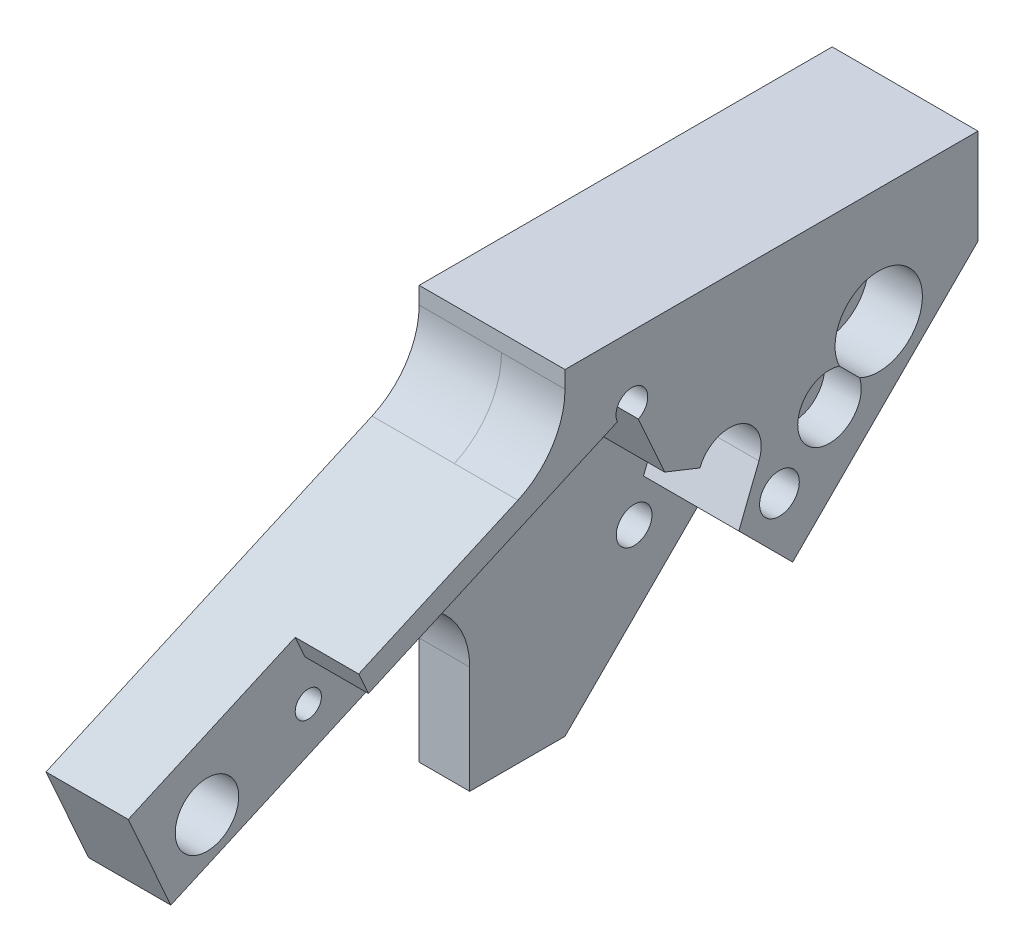
SolidWorks part; units mm, degrees
material "6061 合金"
ref_plane "前视基准面" through (0, 0, 0) normal (0, 0, 1) x (1, 0, 0)
ref_plane "上视基准面" through (0, 0, 0) normal (0, 1, 0) x (1, 0, 0)
ref_plane "右视基准面" through (0, 0, 0) normal (1, 0, 0) x (0, 0, -1)
sketch "草图1" plane through (0, 0, 0) normal (1, 0, 0) x (0, 0, -1)
  line L1 (-25, 25) -> (25, 25)
  line L2 (-25, 25) -> (-25, -25)
  line L3 (-25, -25) -> (25, -25)
  line L4 (25, 25) -> (25, -25)
  line L5 (-25, 25) -> (25, -25) construction
  line L6 (-25, -25) -> (25, 25) construction
  point P0 (0, 0)
  dimension "D1" = 50
  dimension "D2" = 50
extrude "凸台-拉伸1" add sketch "草图1" along normal offset from surface (15.3638 mm away) 8
sketch "草图2" plane through (0, 0, 0) normal (-1, 0, 0) x (0, 0, 1)
  line L0 (25, 25) -> (25, -25) construction
  line L1 (-25, 25) -> (25, 25) construction
  line L2 (25, 25) -> (25, -25)
  line L3 (-25, 25) -> (25, 25)
  line L4 (-25, 27) -> (27, 27)
  line L5 (27, 27) -> (27, -25)
  line L6 (-25, 27) -> (-25, 25)
  line L7 (27, -25) -> (25, -25)
  dimension "D1" = 2
extrude "凸台-拉伸2" add sketch "草图2" along normal blind 3 and the other way up to surface (15.3638 mm away) other way up to face at (15.3638, 0, 0)
sketch "草图3" plane through (-3, 0, 0) normal (-1, 0, 0) x (0, 0, 1)
  circle A0 centre (25, 25) radius 1
extrude "切除-拉伸1" cut sketch "草图3" against normal up to surface (3 mm away) up to face at (0, 0, 0)
sketch "草图4" plane through (15.3638, 0, 0) normal (1, 0, 0) x (0, 0, -1)
  circle A0 centre (0, 0) radius 2.2718
sketch "草图5" plane through (15.3638, 0, 0) normal (1, 0, 0) x (0, 0, -1)
  line L0 (-32.6169, 1.449) -> (-65.893, -13.3665) construction
  line L1 (-36.7494, 10.7306) -> (-70.0254, -4.0848) construction
  line L2 (-32.6169, 1.449) -> (-65.893, -13.3665)
  line L3 (-36.7494, 10.7306) -> (-70.0254, -4.0848)
  line L4 (25, -4.0848) -> (15.6172, 2.7629) construction
  line L5 (25, -25) -> (25, 27) construction
  line L6 (15.6172, 2.7629) -> (5.608, -7) construction
  line L7 (5.608, -7) -> (11.6662, -24.8793) construction
  line L8 (-27.1271, -24.8793) -> (22.3729, -24.8793) construction
  line L9 (-18.323, 18.2395) -> (-14.4489, 9.5379) construction
  line L10 (-18.323, 18.2395) -> (-14.4489, 9.5379)
  circle A0 centre (-64.0834, -7) radius 2.3812 construction
  circle A1 centre (-42.1556, 2.7629) radius 2.3812 construction
  circle A2 centre (-51.3212, -1.3179) radius 2.3813 construction
  circle A3 centre (-64.0834, -7) radius 2.3813
  circle A4 centre (-42.1556, 2.7629) radius 2.3813
  circle A5 centre (-51.3212, -1.3179) radius 2.3813
hole_wizard "M6 螺纹孔1" positions "3D草图1" profile "草图6" tap size "M6" standard "GB" end condition through all
sketch3d "3D草图1"
  point P0 (15.3638, 0, 0)
sketch "草图6" plane through (15.3638, 0, 0) normal (0, 1, 0) x (0, 0, -1)
  line L0 (0, 0) -> (0, 18.3638)
  line L1 (0, 18.3638) -> (2.5, 18.3638)
  line L2 (2.5, 18.3638) -> (2.5, 0)
  line L5 (2.5, 0) -> (0, 0)
  line L11 (0, -6.35) -> (0, 107.95) construction
  dimension "通孔螺纹孔钻头直径" = 5
  dimension "通孔螺纹孔钻头深度" = 18.3638
cosmetic thread "孔螺蚊线1" parameters "D2"=6
sketch "草图7" plane through (15.3638, 0, 0) normal (1, 0, 0) x (0, 0, -1)
  line L1 (-6.3, 6.3) -> (6.3, 6.3) construction
  line L2 (-6.3, 6.3) -> (-6.3, -6.3) construction
  line L3 (-6.3, -6.3) -> (6.3, -6.3) construction
  line L4 (6.3, 6.3) -> (6.3, -6.3) construction
  line L5 (-6.3, 6.3) -> (6.3, -6.3) construction
  line L6 (-6.3, -6.3) -> (6.3, 6.3) construction
  line L7 (-12.5, 12.5) -> (12.5, 12.5) construction
  line L8 (-12.5, 12.5) -> (-12.5, -12.5) construction
  line L9 (-12.5, -12.5) -> (12.5, -12.5) construction
  line L10 (12.5, 12.5) -> (12.5, -12.5) construction
  line L11 (-12.5, 12.5) -> (12.5, -12.5) construction
  line L12 (-12.5, -12.5) -> (12.5, 12.5) construction
  point P0 (0, 0)
  point P6 (0, 0)
  dimension "D1" = 12.6
  dimension "D2" = 25
hole_wizard "打孔尺寸(%根据)内六角圆柱头螺钉的类型2" positions "3D草图3" profile "草图8" counterbore size "M4" standard "GB" end condition through all
sketch3d "3D草图3"
  point P0 (15.3638, 6.3, -6.3)
  point P3 (15.3638, 6.3, 6.3)
  point P10 (15.3638, -6.3, 6.3)
sketch "草图8" plane through (15.3638, 6.3, -6.3) normal (0, 1, 0) x (0, 0, -1)
  line L0 (0, 0) -> (0, 18.3638)
  line L1 (0, 18.3638) -> (2.25, 18.3638)
  line L3 (2.25, 18.3638) -> (2.25, 4.6)
  line L4 (2.25, 4.6) -> (4, 4.6)
  line L5 (4, 4.6) -> (4, 0)
  line L7 (4, 0) -> (0, 0)
  line L11 (0, -6.35) -> (0, 107.95) construction
  dimension "通孔孔直径" = 4.5
  dimension "通孔孔深度" = 18.3638
  dimension "柱形沉头孔直径" = 8
  dimension "柱形沉头孔深度" = 4.6
hole_wizard "打孔尺寸(%根据)内六角圆柱头螺钉的类型2" positions "3D草图4" profile "草图9" counterbore size "M6" standard "GB" end condition through all
sketch3d "3D草图4"
  point P0 (15.3638, 12.5, -12.5)
sketch "草图9" plane through (15.3638, 12.5, -12.5) normal (0, 1, 0) x (0, 0, -1)
  line L0 (0, 0) -> (0, 18.3638)
  line L1 (0, 18.3638) -> (3.3, 18.3638)
  line L3 (3.3, 18.3638) -> (3.3, 6.8)
  line L4 (3.3, 6.8) -> (5.5, 6.8)
  line L5 (5.5, 6.8) -> (5.5, 0)
  line L7 (5.5, 0) -> (0, 0)
  line L11 (0, -6.35) -> (0, 107.95) construction
  dimension "通孔孔直径" = 6.6
  dimension "通孔孔深度" = 18.3638
  dimension "柱形沉头孔直径" = 11
  dimension "柱形沉头孔深度" = 6.8
sketch "草图10" plane through (15.3638, 0, 0) normal (1, 0, 0) x (0, 0, -1)
  line L0 (25, -25) -> (25, 15)
  line L1 (25, -25) -> (25, 27) construction
  line L2 (25, 15) -> (-15, -25)
  line L3 (-27, -25) -> (25, -25) construction
  line L4 (-15, -25) -> (25, -25)
  dimension "D1" = 40
extrude "切除-拉伸2" cut sketch "草图10" against normal through all
sketch "草图11" plane through (15.3638, 0, 0) normal (1, 0, 0) x (0, 0, -1)
  line L0 (-70.0254, -4.0848) -> (-65.893, -13.3665)
  line L1 (-65.893, -13.3665) -> (-27, 3.9498)
  line L2 (-27, -25) -> (-27, 27) construction
  line L3 (-27, 3.9498) -> (-27, 15.0713)
  line L4 (-27, 15.0713) -> (-70.0254, -4.0848)
extrude "凸台-拉伸3" add sketch "草图11" against normal up to surface (18.3638 mm away) up to face at (-3, 11.3153, 11.3153)
sketch "草图16" plane through (15.3638, 0, 0) normal (1, 0, 0) x (0, 0, -1)
  line L0 (-70.0254, -4.0848) -> (-65.893, -13.3665)
  line L1 (-70.0254, -4.0848) -> (-18.5813, 18.8196)
  line L2 (-65.893, -13.3665) -> (-14.4489, 9.5379)
  line L3 (-18.5813, 18.8196) -> (-14.4489, 9.5379)
  line L4 (-18.323, 18.2395) -> (-14.4489, 9.5379) construction
extrude "切除-拉伸3" cut sketch "草图16" against normal blind 8
hole_wizard "M4 螺纹孔1" positions "3D草图5" profile "草图12" tap size "M4" standard "GB" end condition through all
sketch3d "3D草图5"
  point P3 (15.3638, -1.3179, 51.3212)
  point P6 (15.3638, 2.7629, 42.1556)
sketch "草图12" plane through (15.3638, -1.3179, 51.3212) normal (0, 1, 0) x (0, 0, -1)
  line L0 (0, 0) -> (0, 18.3638)
  line L1 (0, 18.3638) -> (1.65, 18.3638)
  line L2 (1.65, 18.3638) -> (1.65, 0)
  line L5 (1.65, 0) -> (0, 0)
  line L11 (0, -6.35) -> (0, 107.95) construction
  dimension "通孔螺纹孔钻头直径" = 3.3
  dimension "通孔螺纹孔钻头深度" = 18.3638
cosmetic thread "孔螺蚊线2" parameters "D2"=4
cosmetic thread "孔螺蚊线3" parameters "D2"=4
fillet "圆角1" radius 10 1 edges at (2.1819, 3.9498, 27)
sketch "草图13" plane through (15.3638, 0, 0) normal (1, 0, 0) x (0, 0, -1)
  line L0 (-70.0254, -4.0848) -> (-65.893, -13.3665) construction
  line L1 (-70.0254, -4.0848) -> (-65.893, -13.3665)
  line L2 (-36.7494, 10.7306) -> (-70.0254, -4.0848) construction
  line L3 (-36.7494, 10.7306) -> (-70.0254, -4.0848)
  line L4 (-37.9696, 13.4712) -> (-73.9863, -2.5644)
  line L5 (-73.9863, -2.5644) -> (-68.6336, -14.5867)
  line L6 (-37.9696, 13.4712) -> (-36.7494, 10.7306)
  line L7 (-68.6336, -14.5867) -> (-65.893, -13.3665)
  dimension "D1" = 3
extrude "凸台-拉伸4" add sketch "草图13" against normal up to surface (18.3638 mm away) up to face at (-3, -1.3179, 49.6712)
sketch "草图17" plane through (7.3638, 0, 0) normal (1, 0, 0) x (0, 0, -1)
  line L0 (-18.5813, 18.8196) -> (-22.2235, 27)
  line L1 (-27, 27) -> (25, 27) construction
  line L2 (-22.2235, 27) -> (-27, 27)
  line L3 (-27, 27) -> (-27, 15.0713)
  line L4 (-27, 15.0713) -> (-18.5813, 18.8196)
  line L5 (-65.893, -13.3665) -> (-68.6336, -14.5867)
  line L6 (-65.893, -13.3665) -> (-71.6564, -0.4216)
  line L7 (-68.6336, -14.5867) -> (-74.397, -1.6418)
  line L8 (-71.6564, -0.4216) -> (-74.397, -1.6418)
extrude "切除-拉伸6" cut sketch "草图17" along normal through all
sketch "草图18" plane through (0, 13.3288, 5.9344) normal (0, 0.9135, 0.4067) x (1, 0, 0)
  line L1 (7.3638, -9.3203) -> (18.2882, -9.3203)
  line L2 (7.3638, -9.3203) -> (7.3638, -36.1151)
  line L3 (7.3638, -36.1151) -> (18.2882, -36.1151)
  line L4 (18.2882, -9.3203) -> (18.2882, -36.1151)
extrude "切除-拉伸8" cut sketch "草图18" against normal through all
sketch "草图19" plane through (7.3638, 0, 0) normal (1, 0, 0) x (0, 0, -1)
  line L0 (-12.5, -12.5) -> (12.5, -12.5) construction
hole_wizard "打孔尺寸(%根据)内六角圆柱头螺钉的类型3" [suppressed] positions "3D草图6" profile "草图20" counterbore size "M6" standard "GB"
sketch3d "3D草图6"
  point P0 (7.3638, -12.5, 12.5)
sketch "草图20" plane through (7.3638, -12.5, 12.5) normal (0, 1, 0) x (0, 0, -1)
  line L0 (0, 0) -> (0, 10.3638)
  line L1 (0, 10.3638) -> (3.3, 10.3638)
  line L3 (3.3, 10.3638) -> (3.3, 5)
  line L4 (3.3, 5) -> (5.5, 5)
  line L5 (5.5, 5) -> (5.5, 0)
  line L7 (5.5, 0) -> (0, 0)
  line L11 (0, -6.35) -> (0, 107.95) construction
  dimension "通孔孔直径" = 6.6
  dimension "通孔孔深度" = 10.3638
  dimension "柱形沉头孔直径" = 11
  dimension "柱形沉头孔深度" = 5
sketch "草图21" plane through (10.7638, 0, 0) normal (1, 0, 0) x (0, 0, -1)
  line L2 (-8.7909, -3.1702) -> (-8.0351, -4.8676)
  line L3 (-6.3965, -8.5479) -> (-5.6408, -10.2453)
  line L4 (-8.7909, -3.1702) -> (-8.0351, -4.8676)
  line L5 (-6.3965, -8.5479) -> (-5.6408, -10.2453)
  arc A2 (-5.6408, -10.2453) -> (-8.7909, -3.1702) centre (-6.3, -6.3) ccw
  arc A3 (-6.3965, -8.5479) -> (-8.0351, -4.8676) centre (-6.3, -6.3) ccw
  arc A4 (-5.6408, -10.2453) -> (-8.7909, -3.1702) centre (-6.3, -6.3) ccw
  arc A5 (-6.3965, -8.5479) -> (-8.0351, -4.8676) centre (-6.3, -6.3) ccw
  dimension "D1" = 0
extrude "切除-拉伸9" cut sketch "草图21" against normal up to surface (3.4 mm away) up to face at (7.3638, -1.3179, 52.9712)
sketch "草图22" plane through (7.3638, 0, 0) normal (1, 0, 0) x (0, 0, -1)
  line L0 (-38.814, -1.6147) -> (-14.4489, 9.5379)
  line L1 (-18.323, 18.2395) -> (-14.4489, 9.5379) construction
  line L2 (-14.4489, 9.5379) -> (-3.9786, -13.9786)
  line L3 (-3.9786, -13.9786) -> (-15, -25)
  line L4 (-15, -25) -> (-27, -25)
  line L5 (-27, -25) -> (-27, -11.4488)
  arc A0 (-27, -11.4488) -> (-38.814, -1.6147) centre (-37, -11.4488) ccw construction
  arc A1 (-27, -11.4488) -> (-38.814, -1.6147) centre (-37, -11.4488) ccw
extrude "切除-拉伸11" cut sketch "草图22" against normal blind 4
sketch "草图23" plane through (15.3638, 0, 0) normal (1, 0, 0) x (0, 0, -1)
  line L0 (-14.4489, 9.5379) -> (-6.3, 6.3)
  line L3 (-3.9786, -13.9786) -> (-14.4489, 9.5379)
  line L4 (-6.3, 6.3) -> (-2.5827, 4.8229)
  line L5 (-2.5827, 4.8229) -> (-5.1161, -1.5529)
  line L6 (-5.1161, -1.5529) -> (1.6655, -8.3345)
  line L7 (-3.9786, -13.9786) -> (1.6655, -8.3345)
  line L8 (25, 15) -> (-3.9786, -13.9786) construction
  circle A0 centre (-6.3, 6.3) radius 4 construction
  dimension "D1" = 33
extrude "切除-拉伸12" cut sketch "草图23" against normal up to surface (12 mm away) up to face at (3.3638, -9.8323, 17.4385)
sketch "草图24" plane through (10.7638, 0, 0) normal (1, 0, 0) x (0, 0, -1)
  line L1 (-10.0173, 7.7771) -> (-8.391, 7.1308)
  line L2 (-10.0173, 7.7771) -> (-8.391, 7.1308)
  line L4 (-4.209, 5.4692) -> (-2.5827, 4.8229)
  line L5 (-4.209, 5.4692) -> (-2.5827, 4.8229)
  arc A1 (-2.5827, 4.8229) -> (-10.0173, 7.7771) centre (-6.3, 6.3) ccw
  arc A2 (-2.5827, 4.8229) -> (-10.0173, 7.7771) centre (-6.3, 6.3) ccw
  arc A4 (-4.209, 5.4692) -> (-8.391, 7.1308) centre (-6.3, 6.3) ccw
  arc A5 (-4.209, 5.4692) -> (-8.391, 7.1308) centre (-6.3, 6.3) ccw
  dimension "D1" = 0
extrude "切除-拉伸13" cut sketch "草图24" against normal blind 4
sketch "草图25" plane through (0, -11.8798, 26.6826) normal (0, 0.4067, -0.9135) x (-1, 0, 0)
  line L5 (3, 24.7502) -> (3, 27.7502)
  line L6 (3, 27.7502) -> (-15.3638, 27.7502)
  line L7 (-15.3638, 27.7502) -> (-15.3638, 24.7502)
  line L8 (-15.3638, 24.7502) -> (-7.3638, 24.7502)
  line L9 (-7.3638, 24.7502) -> (3, 24.7502)
  line L10 (3, 24.7502) -> (3, 27.7502)
  line L11 (3, 27.7502) -> (-15.3638, 27.7502)
  line L12 (-15.3638, 27.7502) -> (-15.3638, 24.7502)
  line L13 (-15.3638, 24.7502) -> (-7.3638, 24.7502)
  line L15 (-7.3638, 24.7502) -> (3, 24.7502)
  dimension "D1" = 0
extrude "凸台-拉伸7" add sketch "草图25" along normal up to surface (10.672 mm away) up to face at (2.1819, 21.0357, 27)
fillet "圆角2" radius 10 1 edges at (2.1819, 18.3552, 27)
sketch "草图26" plane through (7.3638, 0, 0) normal (1, 0, 0) x (0, 0, -1)
  line L0 (-27, 15.0713) -> (-18.5813, 18.8196)
  line L1 (-18.5813, 18.8196) -> (-22.2235, 27)
  line L2 (-22.2235, 27) -> (-27, 27)
  line L4 (-27, 27) -> (-27, 24.8493)
  line L5 (-27, 18.3552) -> (-71.2456, -1.3442) construction
  line L6 (-27, 15.0713) -> (-27, 18.3552) construction
  line L7 (-27, 18.3552) -> (-71.2456, -1.3442)
  line L8 (-27, 15.0713) -> (-27, 18.3552)
  arc A0 (-32.9326, 15.7138) -> (-27, 24.8493) centre (-37, 24.8493) ccw construction
  arc A1 (-32.9326, 15.7138) -> (-27, 24.8493) centre (-37, 24.8493) ccw
  line M6 (-14.4489, 9.5379) -> (-22.2235, 27)
  line M7 (-22.2235, 27) -> (-27, 27)
  line M8 (-27, 27) -> (-27, 24.8493)
  arc M9 (-27, 24.8493) -> (-32.9326, 15.7138) centre (-37, 24.8493) cw
  line M10 (-32.9326, 15.7138) -> (-27, 18.3552)
  line M11 (-27, 18.3552) -> (-27, 15.0713)
extrude "凸台-拉伸8" add sketch "草图26" along normal up to surface (8 mm away) contours L0 M11 M6 M7 M8 M9 M10 up to face at (15.3638, 6.9994, 48.8178)
sketch "草图27" plane through (15.3638, 0, 0) normal (1, 0, 0) x (0, 0, -1)
  circle A0 centre (-18.5813, 18.8196) radius 2
extrude "切除-拉伸14" cut sketch "草图27" against normal up to surface (8 mm away) up to face at (7.3638, -1.3179, 52.9712)
sketch "草图28" plane through (7.3638, 0, 0) normal (1, 0, 0) x (0, 0, -1)
  circle A0 centre (-64.0834, -7) radius 2.3813 construction
  circle A1 centre (-64.0834, -7) radius 2.3813
hole_wizard "打孔尺寸(%根据)内六角圆柱头螺钉的类型4" positions "3D草图7" profile "草图29" counterbore size "M4" standard "GB" end condition through all
sketch3d "3D草图7"
  point P0 (7.3638, -7, 64.0834)
sketch "草图29" plane through (7.3638, -7, 64.0834) normal (0, 1, 0) x (0, 0, -1)
  line L0 (0, 0) -> (0, 10.3638)
  line L1 (0, 10.3638) -> (2.25, 10.3638)
  line L3 (2.25, 10.3638) -> (2.25, 6)
  line L4 (2.25, 6) -> (4, 6)
  line L5 (4, 6) -> (4, 0)
  line L7 (4, 0) -> (0, 0)
  line L11 (0, -6.35) -> (0, 107.95) construction
  dimension "通孔孔直径" = 4.5
  dimension "通孔孔深度" = 10.3638
  dimension "柱形沉头孔直径" = 8
  dimension "柱形沉头孔深度" = 6
sketch "草图30" plane through (15.3638, 0, 0) normal (1, 0, 0) x (0, 0, -1)
  line L11 (-17.7678, 16.9925) -> (-14.4489, 9.5379)
  line L12 (-14.4489, 9.5379) -> (-10.0173, 7.7771)
  line L13 (-2.5827, 4.8229) -> (-5.1161, -1.5529)
  line L14 (-5.1161, -1.5529) -> (1.6655, -8.3345)
  line L15 (1.6655, -8.3345) -> (25, 15)
  line L16 (25, 15) -> (25, 27)
  line L17 (25, 27) -> (-27, 27)
  line L18 (-27, 27) -> (-27, 24.8493)
  line L19 (-32.9326, 15.7138) -> (-71.2456, -1.3442)
  line L20 (-71.2456, -1.3442) -> (-70.0254, -4.0848)
  line L21 (-70.0254, -4.0848) -> (-20.4084, 18.0061)
  line L22 (-17.7678, 16.9925) -> (-14.4489, 9.5379)
  line L23 (-14.4489, 9.5379) -> (-10.0173, 7.7771)
  line L24 (-2.5827, 4.8229) -> (-5.1161, -1.5529)
  line L25 (-5.1161, -1.5529) -> (1.6655, -8.3345)
  line L26 (1.6655, -8.3345) -> (25, 15)
  line L27 (25, 15) -> (25, 27)
  line L28 (25, 27) -> (-27, 27)
  line L29 (-27, 27) -> (-27, 24.8493)
  line L30 (-32.9326, 15.7138) -> (-71.2456, -1.3442)
  line L31 (-71.2456, -1.3442) -> (-70.0254, -4.0848)
  line L32 (-70.0254, -4.0848) -> (-20.4084, 18.0061)
  arc A3 (-17.7678, 16.9925) -> (-20.4084, 18.0061) centre (-18.5813, 18.8196) ccw
  arc A4 (-2.5827, 4.8229) -> (-10.0173, 7.7771) centre (-6.3, 6.3) ccw
  arc A5 (-32.9326, 15.7138) -> (-27, 24.8493) centre (-37, 24.8493) ccw
  arc A6 (-17.7678, 16.9925) -> (-20.4084, 18.0061) centre (-18.5813, 18.8196) ccw
  arc A7 (-2.5827, 4.8229) -> (-10.0173, 7.7771) centre (-6.3, 6.3) ccw
  arc A8 (-32.9326, 15.7138) -> (-27, 24.8493) centre (-37, 24.8493) ccw
  dimension "D1" = 0
extrude "切除-拉伸15" [suppressed] cut sketch "草图30" against normal offset from surface (6 mm away) 2
sketch "草图31" plane through (15.3638, 0, 0) normal (1, 0, 0) x (0, 0, -1)
  line L2 (-38.814, -1.6147) -> (-38.9272, -1.3605)
  line L3 (-38.9272, -1.3605) -> (-41.0674, -2.3134)
  line L4 (-38.814, -1.6147) -> (-38.9272, -1.3605)
  line L5 (-38.9272, -1.3605) -> (-41.0674, -2.3134)
  arc A1 (-38.814, -1.6147) -> (-41.0674, -2.3134) centre (-37, -11.4488) ccw
  arc A2 (-38.814, -1.6147) -> (-41.0674, -2.3134) centre (-37, -11.4488) ccw
  dimension "D1" = 0
extrude "切除-拉伸16" cut sketch "草图31" against normal up to surface (8 mm away) up to face at (7.3638, -7, 60.0834)
sketch "草图32" plane through (0, -26.6953, 59.9586) normal (0, -0.4067, 0.9135) x (1, 0, 0)
  line L4 (15.3638, 24.7502) -> (15.3638, 27.7502)
  line L5 (15.3638, 27.7502) -> (7.3638, 27.7502)
  line L6 (7.3638, 27.7502) -> (7.3638, 24.7502)
  line L7 (7.3638, 24.7502) -> (15.3638, 24.7502)
  line L8 (15.3638, 24.7502) -> (15.3638, 27.7502)
  line L9 (15.3638, 27.7502) -> (7.3638, 27.7502)
  line L10 (7.3638, 27.7502) -> (7.3638, 24.7502)
  line L11 (7.3638, 24.7502) -> (15.3638, 24.7502)
  dimension "D1" = 0
extrude "切除-拉伸17" cut sketch "草图32" against normal blind 20
